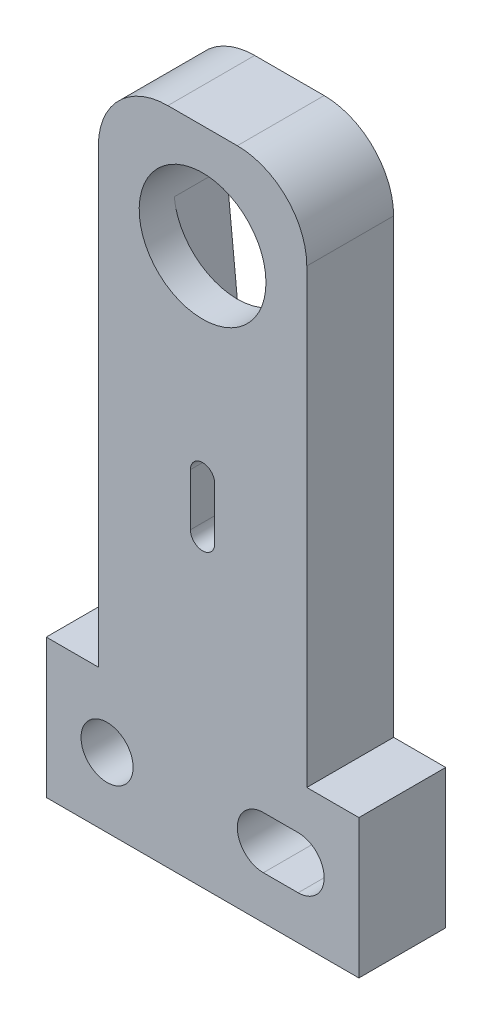
SolidWorks part; units mm, degrees
material "ABS"
ref_plane "Plano frontal" through (0, 0, 0) normal (0, 0, 1) x (1, 0, 0)
ref_plane "Plano superior" through (0, 0, 0) normal (0, 1, 0) x (1, 0, 0)
ref_plane "Plano direito" through (0, 0, 0) normal (1, 0, 0) x (0, 0, -1)
sketch "Esboço1" plane through (0, 0, 0) normal (0, 0, 1) x (1, 0, 0)
  line L0 (0, 0) -> (0, -24) construction
  line L1 (-6, 2) -> (-6, -24)
  line L2 (6, 2) -> (6, -24)
  line L3 (9, -32) -> (9, -24)
  line L4 (-6, -24) -> (-9, -24)
  line L5 (-9, -32) -> (9, -32)
  line L6 (9, -24) -> (6, -24)
  line L7 (-5.5, -28) -> (5.5, -28) construction
  line L8 (-2, 6) -> (2, 6)
  line L9 (2.2387, -14.225) -> (3.6317, -0.365)
  line L10 (-3.6317, -0.365) -> (-2.2387, -14.225)
  line L11 (0, -14.5) -> (0, -11.5) construction
  line L12 (-0.7, -14.5) -> (-0.7, -11.5)
  line L13 (0.7, -14.5) -> (0.7, -11.5)
  line L14 (5.5, -26.5) -> (3.5, -26.5)
  line L15 (6, 0) -> (6, -24) construction
  line L16 (3.5, -29.5) -> (5.5, -29.5)
  line L17 (-6, 0) -> (-6, -24) construction
  line L18 (-9, -24) -> (-9, -32)
  circle A0 centre (-5.5, -28) radius 1.5
  arc A1 (5.5, -29.5) -> (5.5, -26.5) centre (5.5, -28) ccw
  circle A2 centre (0, 0) radius 3.65
  arc A3 (-2.2387, -14.225) -> (2.2387, -14.225) centre (0, -14) ccw
  arc A4 (-0.7, -14.5) -> (0.7, -14.5) centre (0, -14.5) ccw
  arc A5 (0.7, -11.5) -> (-0.7, -11.5) centre (0, -11.5) ccw
  arc A6 (3.5, -26.5) -> (3.5, -29.5) centre (3.5, -28) ccw
  arc A7 (6, 2) -> (2, 6) centre (2, 2) ccw
  arc A8 (-6, 2) -> (-2, 6) centre (-2, 2) cw
  point P8 (-6, -28)
  point P9 (0, -28)
  point P15 (9, -28)
  point P25 (0, -13)
  point P37 (0, -32)
  point P45 (-6, 6)
  dimension "D3" = 3
  dimension "D8" = 7.3
  dimension "D11" = 4.5
  dimension "D12" = 0.7
  dimension "D16" = 4
  dimension "D4" = 8
  dimension "D6" = 18
  dimension "D7" = 30
  dimension "D9" = 6
  dimension "D10" = 14
  dimension "D13" = 3
  dimension "D14" = 0.5
  dimension "D15" = 2
  dimension "D5" = 8
  dimension "D1" = 6
  dimension "D2" = 6
extrude "Ressalto-extrusão1" add sketch "Esboço1" along normal blind 5 contours L8 L1 L5 L2 A2 L9 A3 L10 A1 A0 | L0 A2 L10 A3 | A2 L0 A3 L9 region at (-0.0546, -16.7666, 0) region at (0, -8.5081, 0)
extrude "Corte-extrusão1" cut sketch "Esboço1<3>" along normal blind 3 contours L10 A3 L9 A2 A5 L13 A4 L12 region at (0, -8.5081, 0)
sketch "Esboço1<3>" plane through (0, 0, 0) normal (0, 0, 1) x (1, 0, 0) same geometry as "Esboço1"
equation "\"D2@Esboço1\"=\"D1@Esboço1\""
